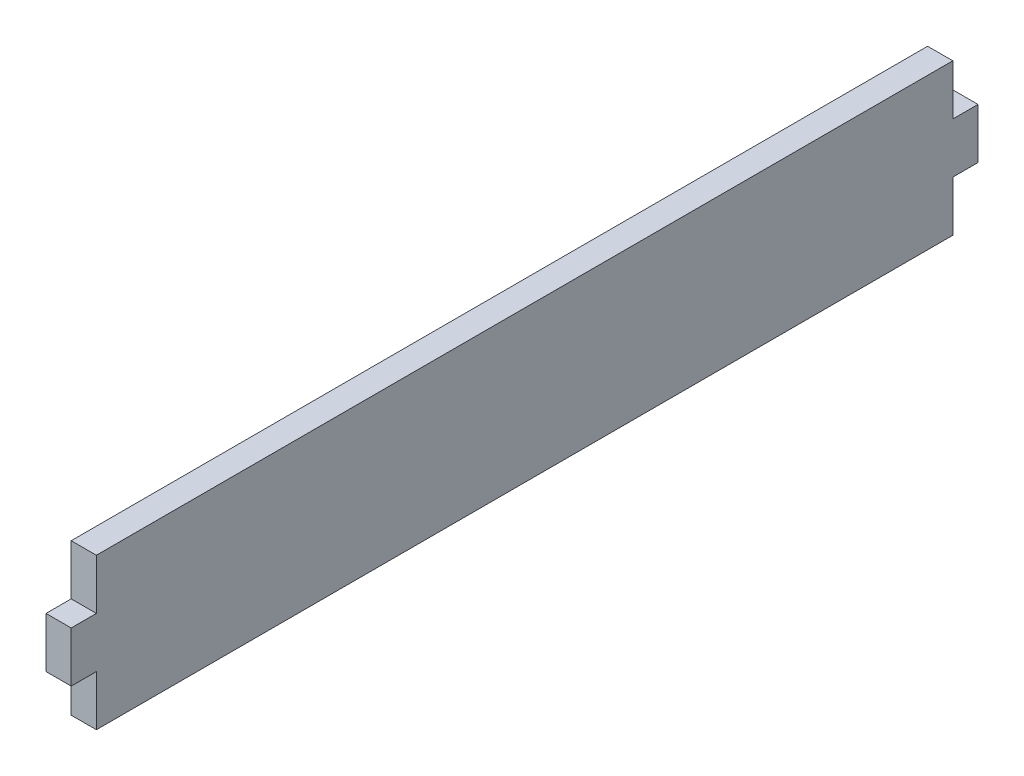
SolidWorks part; units mm, degrees
ref_plane "Front Plane" through (0, 0, 0) normal (0, 0, 1) x (1, 0, 0)
ref_plane "Top Plane" through (0, 0, 0) normal (0, 1, 0) x (1, 0, 0)
ref_plane "Right Plane" through (0, 0, 0) normal (1, 0, 0) x (0, 0, -1)
sketch "Sketch1" plane through (0, 0, 0) normal (1, 0, 0) x (0, 0, -1)
  line L0 (-43.18, 7.62) -> (-43.18, 2.54)
  line L1 (-43.18, 7.62) -> (43.18, 7.62)
  line L2 (-43.18, 7.62) -> (-43.18, -7.62) construction
  line L3 (-43.18, -7.62) -> (43.18, -7.62)
  line L4 (43.18, 7.62) -> (43.18, -7.62) construction
  line L5 (-43.18, 7.62) -> (43.18, -7.62) construction
  line L6 (-43.18, -7.62) -> (43.18, 7.62) construction
  line L7 (-43.18, 2.54) -> (-45.72, 2.54)
  line L8 (-45.72, 2.54) -> (-45.72, -2.54)
  line L9 (-45.72, -2.54) -> (-43.18, -2.54)
  line L10 (-43.18, -2.54) -> (-43.18, -7.62)
  line L11 (-43.18, 0) -> (43.18, 0) construction
  line L12 (0, 7.62) -> (0, -7.62) construction
  line L13 (43.18, -2.54) -> (43.18, -7.62)
  line L14 (45.72, -2.54) -> (43.18, -2.54)
  line L15 (45.72, 2.54) -> (45.72, -2.54)
  line L16 (43.18, 2.54) -> (45.72, 2.54)
  line L17 (43.18, 7.62) -> (43.18, 2.54)
  point P0 (0, 0)
  dimension "D1" = 86.36
  dimension "D2" = 15.24
  dimension "D3" = 5.08
  dimension "D4" = 2.54
extrude "Boss-Extrude1" add sketch "Sketch1" along normal blind 2.54
